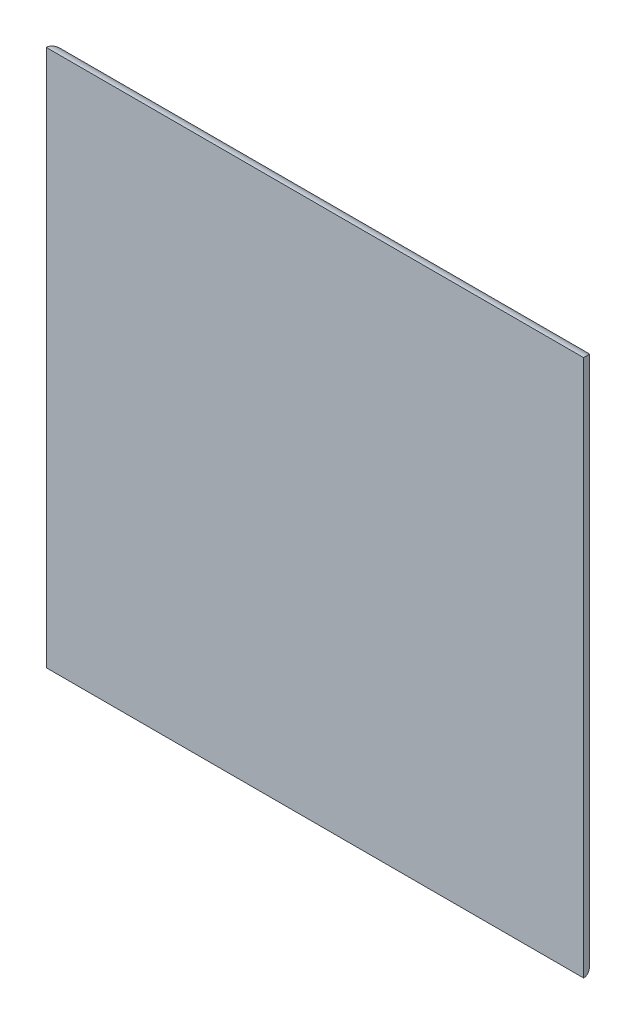
SolidWorks part; units mm, degrees
material "PS HI"
ref_plane "Ön Düzlem" through (0, 0, 0) normal (0, 0, 1) x (1, 0, 0)
ref_plane "Üst Düzlem" through (0, 0, 0) normal (0, 1, 0) x (1, 0, 0)
ref_plane "Sağ Düzlem" through (0, 0, 0) normal (1, 0, 0) x (0, 0, -1)
sketch "Çizim1" plane through (0, 0, 0) normal (0, 0, 1) x (1, 0, 0)
  line L1 (-9, -9) -> (9, -9)
  line L2 (-9, -9) -> (-9, 9)
  line L3 (-9, 9) -> (9, 9)
  line L4 (9, -9) -> (9, 9)
  line L5 (-9, -9) -> (9, 9) construction
  line L6 (-9, 9) -> (9, -9) construction
  point P0 (0, 0)
  dimension "D1" = 18
  dimension "D2" = 18
extrude "Yükseklik-Ekstrüzyon1" add sketch "Çizim1" along normal mid plane 0.5
fillet "Radyus1" radius 0.5 4 edges at (0, -9, -0.25) (-9, 0, -0.25) (0, 9, -0.25) (9, 0, -0.25)
